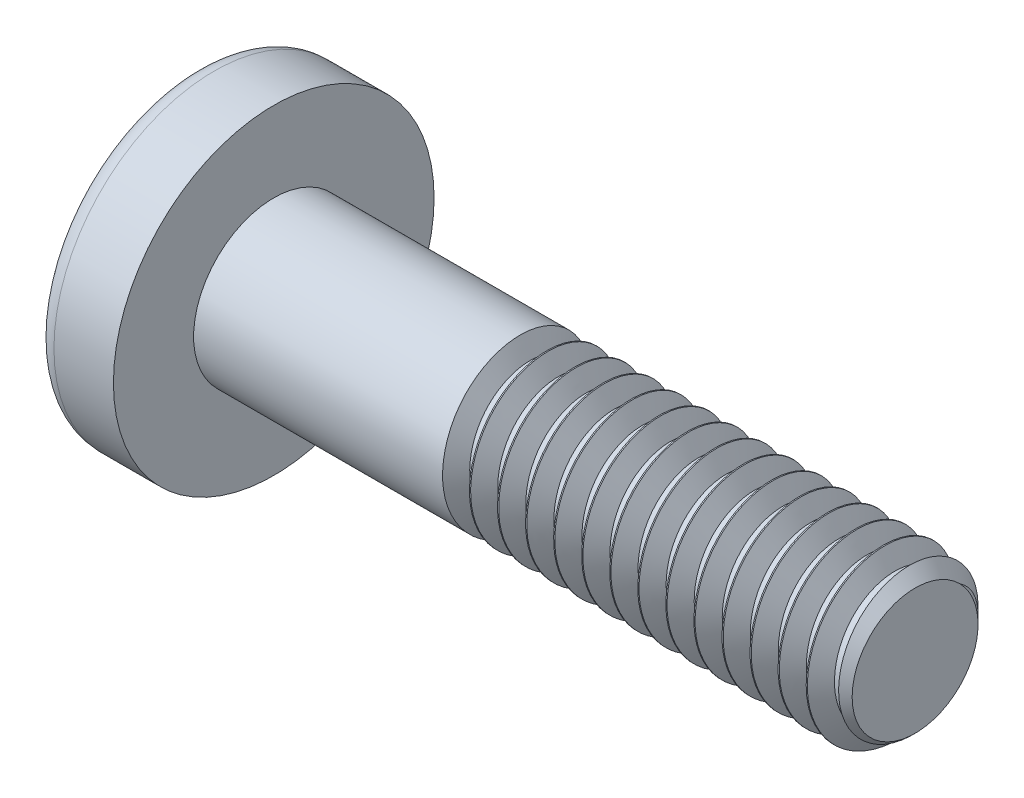
SolidWorks part; units mm, degrees
material "Plain Carbon Steel"
ref_plane "Front Plane" through (0, 0, 0) normal (0, 0, 1) x (1, 0, 0)
ref_plane "Top Plane" through (0, 0, 0) normal (0, 1, 0) x (1, 0, 0)
ref_plane "Right Plane" through (0, 0, 0) normal (1, 0, 0) x (0, 0, -1)
sketch "Sketch1" plane through (0, 0, 0) normal (0, 1, 0) x (1, 0, 0)
  line L0 (-2.9, 2) -> (-2.9, 4)
  line L3 (13.1, 0) -> (-6, 0)
  line L4 (-2.9, 2) -> (13.1, 2)
  line L5 (13.1, 2) -> (13.1, 0)
  line L6 (-4.3836, 4) -> (-2.9, 4)
  arc A0 (-4.773, 3.8007) -> (-6, 0) centre (0.5, 0) ccw
  arc A1 (-4.773, 3.8007) -> (-4.3836, 4) centre (-4.3836, 3.52) cw
  dimension "D5" = 6.5
  dimension "D6" = 0.48
  dimension "D2" = 16
  dimension "D3" = 3.1
revolve "Revolve1" add sketch "Sketch1" angle 360 about L3
chamfer "Chamfer1" distance 0.4295 angle 45 1 edges at (13.1, 0, -2)
ref_plane "Plane1" through (13.8, 0, 0) normal (1, 0, 0) x (0, 0, -1)
sketch "Sketch2" plane through (13.8, 0, 0) normal (1, 0, 0) x (0, 0, -1)
  circle A2 centre (0, 0) radius 1.5705 construction
  circle A3 centre (0, 0) radius 1.5705
curve "Helix/Spiral1" pitch 0.7 height 10.7 radius 1.5705 centre (13.8, 0, 0) axis (-1, 0, 0) start towards (0, 0, -1)
sketch "Sketch3" plane through (0, 0, 0) normal (0, 1, 0) x (1, 0, 0)
  line L0 (12.6705, 2) -> (-2.9, 2) construction
  line L1 (12.6705, 2) -> (-3.0595, 2) construction
  line L3 (13.8, -1.5705) -> (13.8, 1.5705) construction
  line L4 (13.4571, 2.0128) -> (14.1429, 2.0128)
  line L5 (14.1429, 2.0128) -> (13.8875, 1.5705)
  line L6 (13.4571, 2.0128) -> (13.7125, 1.5705)
  line L7 (13.8875, 1.5705) -> (13.7125, 1.5705)
  line L8 (13.8, -1.5705) -> (13.8, 1.5705) construction
  point P11 (13.8, 2.0128)
  point P13 (13.8, 1.5705)
  dimension "D1" = 60
  dimension "D2" = 0.4295
  dimension "D3" = 0.175
sweep "Cut-Sweep1" cut profiles "Sketch3" path "Helix/Spiral1" align with end faces yes
ref_plane "Plane2" through (-6, 0, 0) normal (-1, 0, 0) x (0, 0, 1)
sketch "Sketch4" plane through (-6, 0, 0) normal (-1, 0, 0) x (0, 0, 1)
  line L0 (0.465, -2.2) -> (-0.465, -2.2)
  line L1 (0.465, -2.2) -> (0.465, 2.2)
  line L2 (-0.465, 2.2) -> (0.465, 2.2)
  line L3 (-0.465, 2.2) -> (-0.465, -2.2)
  point P4 (0, 2.2)
  point P5 (0.465, 0)
  point P7 (-0.465, 0)
  point P8 (0, -2.2)
  point P9 (0, 0)
  dimension "D1" = 4.4
  dimension "D2" = 0.93
ref_plane "Plane3" through (-3.583, 0, 0) normal (-1, 0, 0) x (0, 0, 1)
sketch "Sketch5" plane through (-3.583, 0, 0) normal (-1, 0, 0) x (0, 0, 1)
  line L0 (0.2325, -0.2325) -> (-0.2325, -0.2325)
  line L1 (0.2325, -0.2325) -> (0.2325, 0.2325)
  line L2 (-0.2325, 0.2325) -> (0.2325, 0.2325)
  line L3 (-0.2325, 0.2325) -> (-0.2325, -0.2325)
  point P4 (0, 0)
  dimension "D1" = 0.465
  dimension "D2" = 0.465
loft "Cut-Loft1" cut profiles "Sketch5", "Sketch4" connector at (-3.583, -0.2325, -0.2325) connector at (-6, -2.2, -0.465)
pattern_circular "CirPattern1" count 2 every 90 about axis through (13.1, 0, 0) along (1, 0, 0) of "Cut-Loft1"
